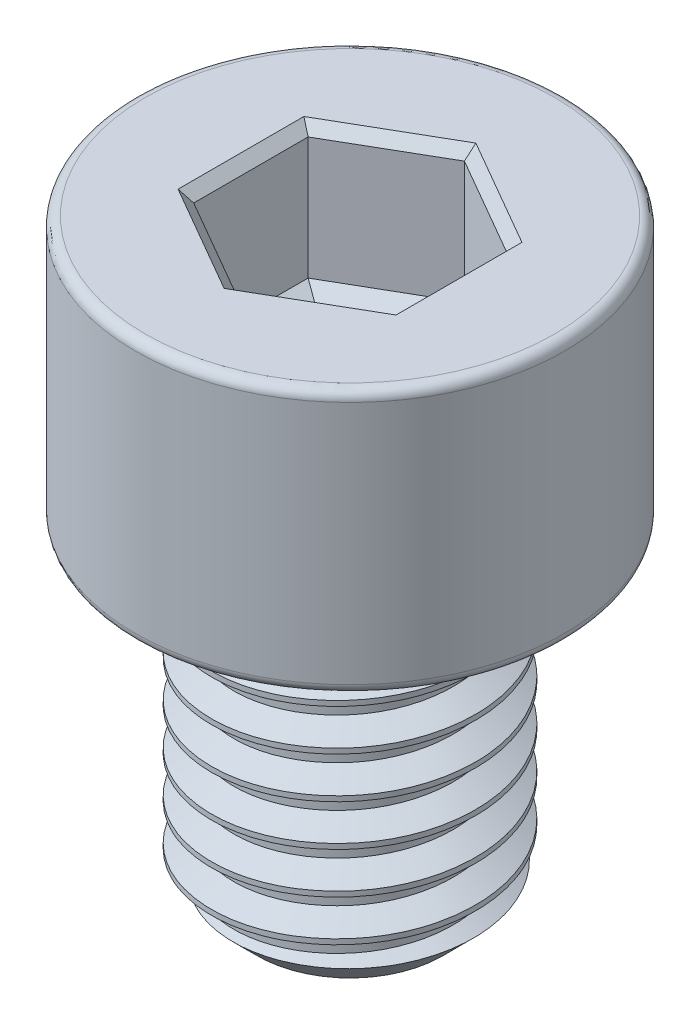
SolidWorks part; units mm, degrees
material "AISI Type A2 Tool Steel"
ref_plane "Front Plane" through (0, 0, 0) normal (0, 0, 1) x (1, 0, 0)
ref_plane "Top Plane" through (0, 0, 0) normal (0, 1, 0) x (1, 0, 0)
ref_plane "Right Plane" through (0, 0, 0) normal (1, 0, 0) x (0, 0, -1)
sketch "Sketch1" plane through (0, 0, 0) normal (0, 1, 0) x (1, 0, 0)
  circle A0 centre (0, 0) radius 4
  dimension "D1" = 8
extrude "Boss-Extrude1" add sketch "Sketch1" along normal blind 10
thread "Thread1" pitch 1.25 method cut profile "Thread Profile1" start angle 0, offset 1.25, length 0, pitch 1.25, diameter 8
ref_plane "Plane1" through (-4, 11.25, 0) normal (0, 0, 1) x (-1, 0, 0)
sketch "Thread Profile1" plane through (-4, 11.25, 0) normal (0, 0, 1) x (-1, 0, 0)
  line L0 (0, 0) -> (0, 1.25) construction
  line L11 (0, 0) -> (0, 1.0937)
  line L12 (0, 1.0937) -> (-0.6766, 0.7031)
  line L13 (-0.6766, 0.7031) -> (-0.6766, 0.3906)
  line L15 (-0.6766, 0.3906) -> (0, 0)
  line L17 (-0.6766, 0.5469) -> (0, 0.5469) construction
  point P2 (0, 0)
  dimension "Pitch" = 1.25
  dimension "Profile_Angle" = 60
  dimension "Profile_Land" = 0.3125
  dimension "Profile_Height" = 0.6766
sketch "Sketch2" plane through (0, 10, 0) normal (0, 1, 0) x (1, 0, 0)
  circle A0 centre (0, 0) radius 6.5
  dimension "D1" = 13
extrude "Boss-Extrude2" add sketch "Sketch2" along normal blind 8
sketch "Sketch5" plane through (0, 0, 0) normal (0, 0, 1) x (1, 0, 0)
  line L0 (0, 0) -> (0, 0.9986) construction
  line L1 (0, 0) -> (4.01, 0) construction
  line L2 (4.01, 0) -> (4.01, 1.2)
  line L3 (4.01, 1.2) -> (2.81, 0)
  line L4 (2.81, 0) -> (4.01, 0)
  dimension "D1" = 1.2
  dimension "D2" = 45
  dimension "D3" = 4.01
revolve "Cut-Revolve1" cut sketch "Sketch5" angle 360 about L0
fillet "Fillet1" radius 0.3 2 edges at (0, 18, 6.5) (0, 10, 6.5)
sketch "Sketch6" plane through (0, 18, 0) normal (0, 1, 0) x (1, 0, 0)
  line L1 (0, 3.4641) -> (-3, 1.7321)
  line L2 (-3, 1.7321) -> (-3, -1.7321)
  line L3 (-3, -1.7321) -> (0, -3.4641)
  line L4 (0, -3.4641) -> (3, -1.7321)
  line L5 (3, -1.7321) -> (3, 1.7321)
  line L6 (3, 1.7321) -> (0, 3.4641)
  circle A0 centre (0, 0) radius 3 construction
  dimension "D1" = 6
extrude "Cut-Extrude1" cut sketch "Sketch6" against normal blind 4
chamfer "Chamfer1" distance 0.3 angle 45 6 edges at (-3, 18, 0) (-1.5, 18, 2.5981) (1.5, 18, 2.5981) (3, 18, 0) (1.5, 18, -2.5981) (-1.5, 18, -2.5981)
sketch "Sketch7" plane through (0, 14, 0) normal (0, 1, 0) x (1, 0, 0)
  line L1 (0, 3.4641) -> (-3, 1.7321)
  line L2 (-3, 1.7321) -> (-3, -1.7321)
  line L3 (-3, -1.7321) -> (0, -3.4641)
  line L4 (0, -3.4641) -> (3, -1.7321)
  line L5 (3, -1.7321) -> (3, 1.7321)
  line L6 (3, 1.7321) -> (0, 3.4641)
  circle A0 centre (0, 0) radius 3 construction
extrude "Cut-Extrude2" cut sketch "Sketch7" against normal blind 0.4 draft 60
